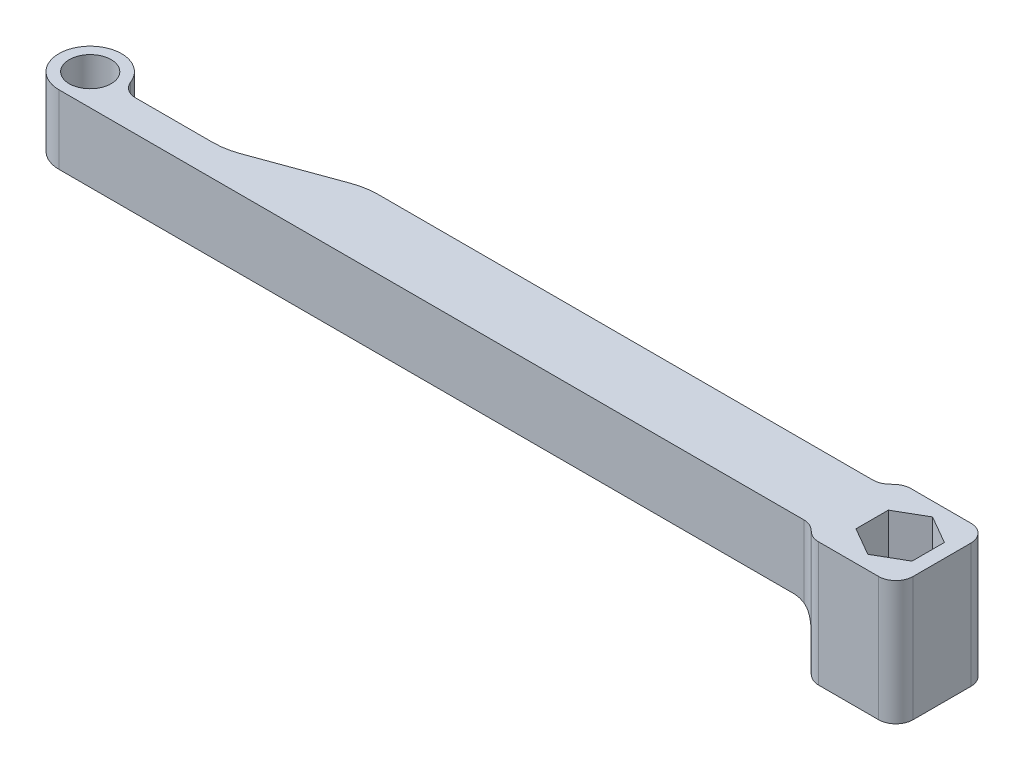
SolidWorks part; units mm, degrees
ref_plane "Front Plane" through (0, 0, 0) normal (0, 0, 1) x (1, 0, 0)
ref_plane "Top Plane" through (0, 0, 0) normal (0, 1, 0) x (1, 0, 0)
ref_plane "Right Plane" through (0, 0, 0) normal (1, 0, 0) x (0, 0, -1)
sketch "Sketch1" plane through (0, 0, 0) normal (0, 1, 0) x (1, 0, 0)
  line L0 (0, 6.075) -> (0, 9.075) construction
  line L1 (9.075, 0) -> (39.075, 0)
  line L3 (0, -9.075) -> (244, -9.075)
  line L7 (39.075, 0) -> (69.0912, 10.925)
  line L8 (9.075, 0) -> (0, 0) construction
  line L9 (244, -9.075) -> (244, 0)
  line L10 (69.0912, 10.925) -> (244, 10.925)
  line L11 (244, 10.925) -> (244, 0)
  circle A0 centre (0, 0) radius 6.075
  circle A1 centre (0, 0) radius 9.075 construction
  arc A6 (9.075, 0) -> (0, -9.075) centre (0, 0) ccw
  dimension "D1" = 12.15
  dimension "D2" = 3
  dimension "D3" = 244
  dimension "D4" = 20
  dimension "D5" = 30
  dimension "D6" = 20
extrude "Boss-Extrude1" add sketch "Sketch1" along normal blind 20
sketch "Sketch5" plane through (0, 20, 0) normal (0, 1, 0) x (1, 0, 0)
  line L0 (234, 0.925) -> (234, -9.075) construction
  line L1 (234, 10.3098) -> (225.8725, 5.6174)
  line L2 (225.8725, 5.6174) -> (225.8725, -3.7674)
  line L3 (225.8725, -3.7674) -> (234, -8.4598)
  line L4 (234, -8.4598) -> (242.1275, -3.7674)
  line L5 (242.1275, -3.7674) -> (242.1275, 5.6174)
  line L6 (242.1275, 5.6174) -> (234, 10.3098)
  line L7 (0, -9.075) -> (244, -9.075) construction
  line L8 (234, 10.925) -> (234, 0.925) construction
  line L9 (244, 10.925) -> (69.0912, 10.925) construction
  line L10 (234, 0.925) -> (244, 0.925) construction
  line L11 (244, -9.075) -> (244, 10.925) construction
  circle A0 centre (234, 0.925) radius 8.1275 construction
  point P18 (244, 0.925)
  dimension "D1" = 16.255
extrude "Cut-Extrude3" cut sketch "Sketch5" against normal through all both and the other way through all
sketch "Sketch6" plane through (0, 20, 0) normal (0, 1, 0) x (1, 0, 0)
  line L0 (244, -9.075) -> (244, 10.925) construction
  line L7 (0, -9.075) -> (244, -9.075) construction
  line L8 (225.8725, 5.6174) -> (225.8725, -3.7674) construction
  line L9 (217.8725, 10.925) -> (221.9064, 14.3098)
  line L10 (221.9064, 14.3098) -> (246.1275, 14.3098)
  line L11 (246.1275, 14.3098) -> (246.1275, -12.4598)
  line L12 (217.8725, 10.925) -> (244, 10.925)
  line L13 (244, 10.925) -> (244, -9.075)
  line L14 (244, 0.925) -> (246.1275, 0.925) construction
  line L15 (217.8725, -9.075) -> (244, -9.075)
  line L16 (221.9064, -12.4598) -> (246.1275, -12.4598)
  line L17 (217.8725, -9.075) -> (221.9064, -12.4598)
  line L18 (242.1275, -3.7674) -> (242.1275, 5.6174) construction
  dimension "D1" = 8
  dimension "D2" = 4
  dimension "D3" = 4
  dimension "D4" = 40
extrude "Boss-Extrude2" add sketch "Sketch6" against normal up to surface (20 mm away) up to face at (234, 0, -0.925)
sketch "Sketch7" plane through (0, 0, 0) normal (0, -1, 0) x (1, 0, 0)
  line L0 (217.8725, 9.075) -> (217.8725, -10.925)
  line L7 (242.1275, -5.6174) -> (242.1275, 3.7674)
  line L8 (234, -10.3098) -> (242.1275, -5.6174)
  line L9 (69.0912, -10.925) -> (217.8725, -10.925)
  line L10 (217.8725, -10.925) -> (221.9064, -14.3098)
  line L11 (221.9064, -14.3098) -> (246.1275, -14.3098)
  line L12 (246.1275, -14.3098) -> (246.1275, 12.4598)
  line L13 (246.1275, 12.4598) -> (221.9064, 12.4598)
  line L14 (221.9064, 12.4598) -> (217.8725, 9.075)
  line L15 (217.8725, 9.075) -> (0, 9.075)
  line L16 (9.075, 0) -> (39.075, 0)
  line L17 (39.075, 0) -> (69.0912, -10.925)
  line L19 (217.8725, -10.925) -> (221.9064, -14.3098)
  line L20 (221.9064, -14.3098) -> (246.1275, -14.3098)
  line L21 (246.1275, -14.3098) -> (246.1275, 12.4598)
  line L22 (246.1275, 12.4598) -> (221.9064, 12.4598)
  line L23 (221.9064, 12.4598) -> (217.8725, 9.075)
  line L27 (225.8725, -5.6174) -> (234, -10.3098)
  line L28 (225.8725, 3.7674) -> (225.8725, -5.6174)
  line L29 (234, 8.4598) -> (225.8725, 3.7674)
  line L30 (242.1275, 3.7674) -> (234, 8.4598)
  line L31 (242.1275, -5.6174) -> (242.1275, 3.7674)
  line L32 (234, -10.3098) -> (242.1275, -5.6174)
  line L33 (225.8725, -5.6174) -> (234, -10.3098)
  line L34 (225.8725, 3.7674) -> (225.8725, -5.6174)
  line L35 (234, 8.4598) -> (225.8725, 3.7674)
  line L36 (242.1275, 3.7674) -> (234, 8.4598)
  arc A1 (0, 9.075) -> (9.075, 0) centre (0, 0) ccw
  dimension "D1" = 0
  dimension "D2" = 0
extrude "Boss-Extrude3" add sketch "Sketch7" along normal offset from surface (12 mm away) 32 up to face at (147.8099, 20, -1.8354)
sketch "Sketch8" plane through (0, -12, 0) normal (0, -1, 0) x (1, 0, 0)
  line L6 (221.9064, -14.3098) -> (246.1275, -14.3098)
  line L7 (246.1275, -14.3098) -> (246.1275, 12.4598)
  line L8 (246.1275, 12.4598) -> (221.9064, 12.4598)
  line L9 (221.9064, 12.4598) -> (217.8725, 9.075)
  line L10 (217.8725, 9.075) -> (217.8725, -10.925)
  line L11 (217.8725, -10.925) -> (221.9064, -14.3098)
  line L12 (221.9064, -14.3098) -> (246.1275, -14.3098)
  line L13 (246.1275, -14.3098) -> (246.1275, 12.4598)
  line L14 (246.1275, 12.4598) -> (221.9064, 12.4598)
  line L15 (221.9064, 12.4598) -> (217.8725, 9.075)
  line L16 (217.8725, 9.075) -> (217.8725, -10.925)
  line L17 (217.8725, -10.925) -> (221.9064, -14.3098)
  dimension "D1" = 0
extrude "Boss-Extrude4" add sketch "Sketch8" along normal blind 4
fillet "Fillet1" radius 5 6 edges at (246.1275, 2, 12.4598) (246.1275, 2, -14.3098) (217.8725, -8, 9.075) (217.8725, -8, -10.925) (221.9064, 2, -14.3098) (221.9064, 2, 12.4598)
fillet "Fillet2" radius 5 3 edges at (218.341, 0, 8.8566) (218.341, 0, -10.7066) (217.8725, 0, -0.925)
fillet "Fillet3" radius 5 2 edges at (217.8725, 8.607, -10.925) (217.8725, 8.607, 9.075)
fillet "Fillet4" radius 20 2 edges at (69.0912, 10, -10.925) (39.075, 10, 0)
fillet "Fillet5" radius 5 1 edges at (9.075, 10, 0)
sketch "Sketch9" plane through (0, 20, 0) normal (0, 1, 0) x (1, 0, 0)
  line L0 (-9.0749, -0.0341) -> (246.1275, 0.925) construction
  line L1 (246.1275, -7.4598) -> (246.1275, 9.3098) construction
  arc A0 (8.4831, 3.2238) -> (0, -9.075) centre (0, 0) ccw construction
